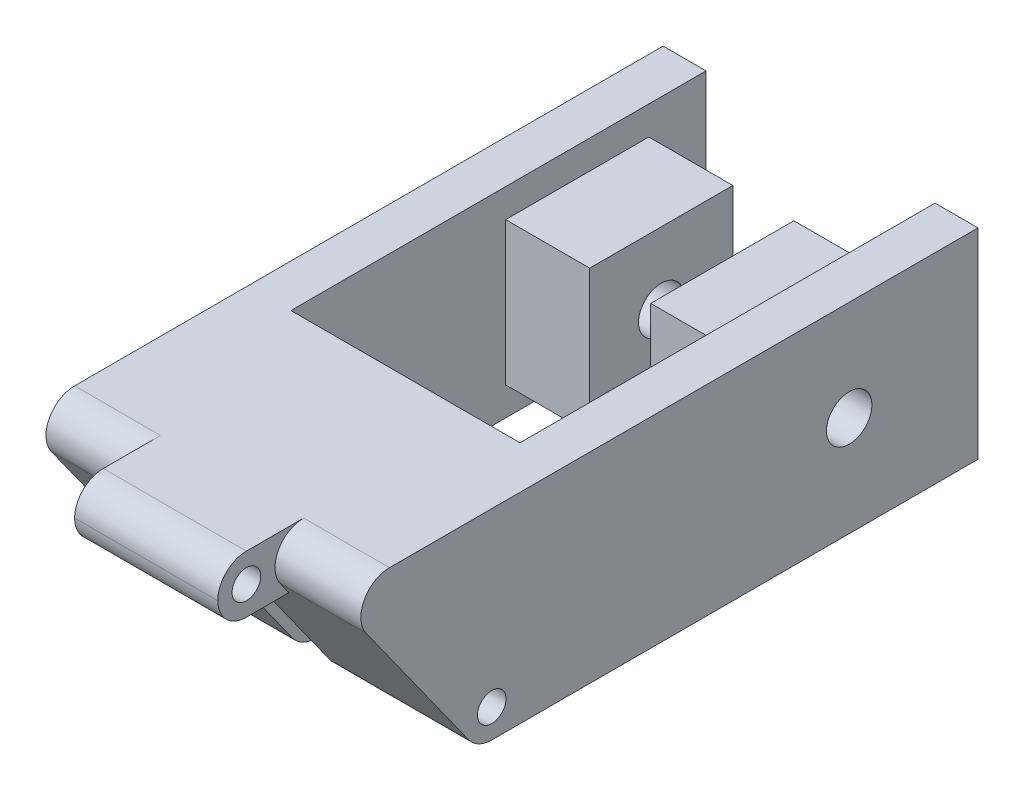
SolidWorks part; units mm, degrees
ref_plane "Front Plane" through (0, 0, 0) normal (0, 0, 1) x (1, 0, 0)
ref_plane "Top Plane" through (0, 0, 0) normal (0, 1, 0) x (1, 0, 0)
ref_plane "Right Plane" through (0, 0, 0) normal (1, 0, 0) x (0, 0, -1)
sketch "Sketch1" plane through (0, 0, 0) normal (1, 0, 0) x (0, 0, -1)
  line L0 (-42.7411, 3.8375) -> (-35.5982, -6.1625)
  line L1 (-33.9708, -7) -> (0, -7)
  line L3 (-41.1136, 7) -> (0, 7)
  line L4 (0, -7) -> (0, 7)
  arc A2 (-35.5982, -6.1625) -> (-33.9708, -7) centre (-33.9708, -5) ccw
  arc A3 (-42.7411, 3.8375) -> (-41.1136, 7) centre (-41.1136, 5) cw
  circle A4 centre (-33.9708, -5) radius 1
  point P0 (0, 0)
  point P2 (0, 0)
  point P11 (0, 7)
  point P14 (-35, -7)
  point P17 (-45, 7)
  dimension "D4" = 2
  dimension "D5" = 2
  dimension "D1" = 14
  dimension "D2" = 45
  dimension "D3" = 10
extrude "Boss-Extrude1" add sketch "Sketch1" along normal mid plane 22
sketch "Sketch2" plane through (0, 7, 0) normal (0, 1, 0) x (1, 0, 0)
  line L0 (11, -41.1136) -> (-11, -41.1136) construction
  line L1 (5, -47.1136) -> (-5, -47.1136)
  line L2 (5, -47.1136) -> (5, -41.1136)
  line L3 (5, -41.1136) -> (-5, -41.1136)
  line L4 (-5, -47.1136) -> (-5, -41.1136)
  line L5 (5, -47.1136) -> (-5, -41.1136) construction
  line L6 (5, -41.1136) -> (-5, -47.1136) construction
  point P0 (0, -44.1136)
  dimension "D1" = 6
  dimension "D2" = 10
extrude "Boss-Extrude2" add sketch "Sketch2" against normal blind 4
sketch "Sketch3" plane through (5, 0, 0) normal (1, 0, 0) x (0, 0, -1)
  line L0 (-47.1136, 3) -> (-47.1136, 7) construction
  line L1 (-47.1136, 3) -> (-42.1429, 3) construction
  circle A0 centre (-45.1136, 5) radius 1
  dimension "D1" = 2
  dimension "D2" = 2
  dimension "D3" = 2
extrude "Cut-Extrude1" cut sketch "Sketch3" against normal up to next
fillet "Fillet1" radius 2 2 edges at (0, 3, 47.1136) (0, 7, 47.1136)
sketch "Sketch4" plane through (0, -7, 0) normal (0, -1, 0) x (1, 0, 0)
  line L0 (11, 35.5982) -> (-11, 35.5982) construction
  line L1 (1.3, 31.5982) -> (-1.3, 31.5982)
  line L2 (1.3, 31.5982) -> (1.3, 39.5982)
  line L3 (1.3, 39.5982) -> (-1.3, 39.5982)
  line L4 (-1.3, 31.5982) -> (-1.3, 39.5982)
  line L5 (1.3, 31.5982) -> (-1.3, 39.5982) construction
  line L6 (1.3, 39.5982) -> (-1.3, 31.5982) construction
  point P0 (0, 35.5982)
  dimension "D1" = 8
  dimension "D2" = 2.6
extrude "Cut-Extrude3" cut sketch "Sketch4" against normal blind 7
ref_plane "Plane1" through (0, 0, 0) normal (-1, 0, 0) x (0, 0, 1)
sketch "Sketch5" plane through (0, 0, 0) normal (-1, 0, 0) x (0, 0, 1)
  line L4 (0, -7) -> (0, 7) construction
  line L5 (-11, -20) -> (29, -20)
  line L6 (-11, -20) -> (-11, 20)
  line L7 (-11, 20) -> (29, 20)
  line L8 (29, -20) -> (29, 20)
  line L9 (-11, -20) -> (29, 20) construction
  line L10 (-11, 20) -> (29, -20) construction
  circle A0 centre (9, 0) radius 1.5875
  dimension "D1" = 3.175
  dimension "D2" = 9
  dimension "D3" = 40
extrude "Cut-Extrude4" cut sketch "Sketch5" along normal mid plane 16 contours L5 L8 L7 L6 | A0 region at (0, 0, -10.4343)
extrude "Cut-Extrude5" cut sketch "Sketch5<3>" against normal mid plane 25 contours A0
sketch "Sketch5<3>" plane through (0, 0, 0) normal (-1, 0, 0) x (0, 0, 1) same geometry as "Sketch5"
sketch "Sketch7" plane through (-8, 0, 0) normal (1, 0, 0) x (0, 0, -1)
  line L1 (-14, -5) -> (-4, -5)
  line L2 (-14, -5) -> (-14, 5)
  line L3 (-14, 5) -> (-4, 5)
  line L4 (-4, -5) -> (-4, 5)
  line L5 (-14, -5) -> (-4, 5) construction
  line L6 (-14, 5) -> (-4, -5) construction
  circle A1 centre (-9, 0) radius 1.5875
  dimension "D1" = 3.175
  dimension "D2" = 10
  dimension "D3" = 10
extrude "Boss-Extrude3" add sketch "Sketch7" along normal blind 5.87
sketch "Sketch9" plane through (8, 0, 0) normal (-1, 0, 0) x (0, 0, 1)
  line L1 (4, -5) -> (14, -5)
  line L2 (4, -5) -> (4, 5)
  line L3 (4, 5) -> (14, 5)
  line L4 (14, -5) -> (14, 5)
  line L5 (4, -5) -> (14, 5) construction
  line L6 (4, 5) -> (14, -5) construction
  circle A0 centre (9, 0) radius 1.5875
  dimension "D1" = 3.175
  dimension "D2" = 10
  dimension "D3" = 10
extrude "Boss-Extrude4" add sketch "Sketch9" along normal blind 5.865
